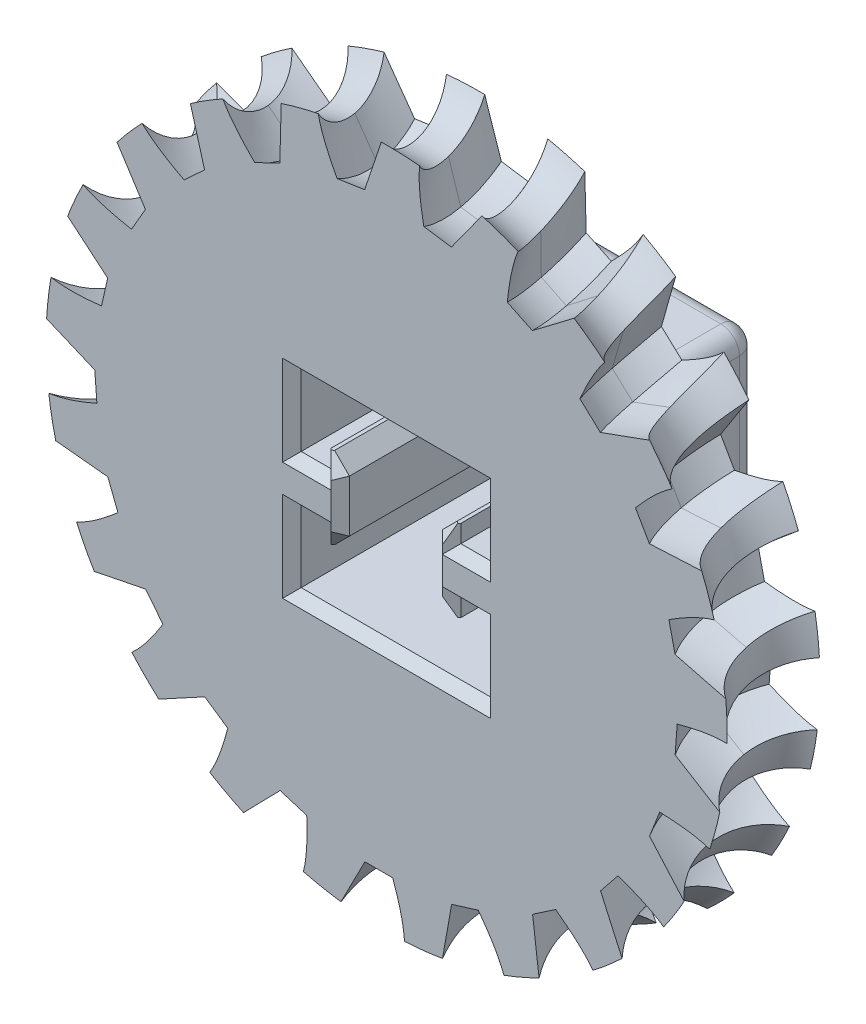
SolidWorks part; units mm, degrees
ref_plane "Front Plane" through (0, 0, 0) normal (0, 0, 1) x (1, 0, 0)
ref_plane "Top Plane" through (0, 0, 0) normal (0, 1, 0) x (1, 0, 0)
ref_plane "Right Plane" through (0, 0, 0) normal (1, 0, 0) x (0, 0, -1)
sketch "Sketch1" plane through (0, 0, 0) normal (0, 0, 1) x (1, 0, 0)
  circle A0 centre (0, 0) radius 40
  circle A1 centre (0, 0) radius 4
  dimension "D1" = 80
  dimension "D2" = 8
extrude "Boss-Extrude1" add sketch "Sketch1" along normal blind 10
chamfer "Chamfer1" distance 2 angle 45 2 edges at (40, 0, 0) (40, 0, 10)
sketch "Sketch2" plane through (0, 0, 0) normal (1, 0, 0) x (0, 0, -1)
  line L0 (0, 0) -> (12.769, 0) construction
  line L1 (0, 0) -> (-5, 0) construction
  line L2 (-5, 0) -> (-5, -40) construction
  circle A0 centre (-5, -40) radius 6
  dimension "D1" = 12
  dimension "D2" = 40
revolve "Cut-Revolve1" cut sketch "Sketch2" angle 360 about L0
sketch "Sketch3" plane through (0, 0, 0) normal (1, 0, 0) x (0, 0, -1)
  circle A1 centre (-5, -40) radius 6
  circle A2 centre (-5, -40) radius 6
  dimension "D1" = 0
curve "Helix/Spiral1" pitch 10 height 2.5 turns 0.25
ref_plane "Plane1" through (0, 0, 5) normal (0, 0, 1) x (1, 0, 0)
sketch "Sketch5" plane through (0, 0, 5) normal (0, 0, 1) x (1, 0, 0)
  line L0 (0, 0) -> (0, -30) construction
  line L1 (-1.5, -30) -> (1.5, -30)
  line L4 (3.5, -34) -> (1.5, -30)
  line L6 (-3.5, -35.5198) -> (3.5, -35.5198)
  line L7 (3.5, -35.5198) -> (3.5, -34)
  line L8 (-3.5, -35.5198) -> (-3.5, -34)
  line L9 (-3.5, -34) -> (-1.5, -30)
  point P9 (0, -35.5198)
  dimension "D1" = 30
  dimension "D2" = 3
  dimension "D3" = 4
  dimension "D4" = 7
sweep "Cut-Sweep1" cut profiles "Sketch5" path "Helix/Spiral1" align with end faces yes
sketch "Sketch6" plane through (0, 0, 0) normal (1, 0, 0) x (0, 0, -1)
  circle A1 centre (-5, -40) radius 6
  circle A2 centre (-5, -40) radius 6
  dimension "D1" = 0
curve "Helix/Spiral2" pitch 10 height 2.5 turns 0.25
sketch "Sketch7" plane through (0, 0, 5) normal (0, 0, 1) x (1, 0, 0)
  line L6 (1.5, -30) -> (-1.5, -30)
  line L7 (3.5, -34) -> (1.5, -30)
  line L8 (3.5, -35.5198) -> (3.5, -34)
  line L9 (-3.5, -35.5198) -> (3.5, -35.5198)
  line L10 (-3.5, -34) -> (-3.5, -35.5198)
  line L11 (-1.5, -30) -> (-3.5, -34)
  line L12 (1.5, -30) -> (-1.5, -30)
  line L13 (3.5, -34) -> (1.5, -30)
  line L14 (3.5, -35.5198) -> (3.5, -34)
  line L15 (-3.5, -35.5198) -> (3.5, -35.5198)
  line L16 (-3.5, -34) -> (-3.5, -35.5198)
  line L17 (-1.5, -30) -> (-3.5, -34)
  dimension "D1" = 0
sweep "Cut-Sweep2" cut profiles "Sketch7" path "Helix/Spiral2" align with end faces yes
pattern_circular "CirPattern1" count 21 over 360 about axis through (0, 0, 10) along (0, 0, -1) of "Cut-Sweep1", "Cut-Sweep2" reverse direction yes
sketch "Sketch14" plane through (0, 0, 0) normal (0, 0, -1) x (-1, 0, 0)
  line L1 (-15, -15) -> (15, -15)
  line L2 (-15, -15) -> (-15, 15)
  line L3 (-15, 15) -> (15, 15)
  line L4 (15, -15) -> (15, 15)
  line L5 (-15, -15) -> (15, 15) construction
  line L6 (-15, 15) -> (15, -15) construction
  point P0 (0, 0)
  dimension "D1" = 30
  dimension "D2" = 30
sketch "Sketch13" plane through (0, 0, 10) normal (0, 0, 1) x (1, 0, 0)
  line L0 (0, -10.2) -> (0, 10.2) construction
  line L1 (10.2, 10.2) -> (-10.2, 10.2) construction
  line L2 (-3.1, 10.2) -> (3.1, 10.2)
  line L3 (-10.2, 10.2) -> (-3.1, 10.2)
  line L9 (-10.2, -10.2) -> (-10.2, 10.2) construction
  line L10 (10.2, 0) -> (-10.2, 0) construction
  line L11 (-5, 2.8) -> (-5, -2.8)
  line L12 (-6.6, 4.4) -> (-5, 2.8)
  line L13 (-7, 4.4) -> (-6.6, 4.4)
  line L14 (-7, 2.5) -> (-7, 4.4)
  line L15 (-10.2, 2.5) -> (-7, 2.5)
  line L16 (-10.2, 10.2) -> (-10.2, 2.5)
  line L17 (10.2, -10.2) -> (10.2, 10.2) construction
  line L18 (10.2, 10.2) -> (0, 0) construction
  line L19 (10.2, 10.2) -> (10.2, 2.5)
  line L20 (10.2, 2.5) -> (7, 2.5)
  line L21 (7, 2.5) -> (7, 4.4)
  line L22 (7, 4.4) -> (6.6, 4.4)
  line L23 (6.6, 4.4) -> (5, 2.8)
  line L24 (5, 2.8) -> (5, -2.8)
  line L29 (10.2, 10.2) -> (3.1, 10.2)
  line L30 (10.2, -10.2) -> (0, 0) construction
  line L31 (-10.2, -10.2) -> (0, 0) construction
  line L32 (10.2, -10.2) -> (-10.2, -10.2) construction
  line L33 (10.2, -10.2) -> (3.1, -10.2)
  line L38 (6.6, -4.4) -> (5, -2.8)
  line L39 (7, -4.4) -> (6.6, -4.4)
  line L40 (7, -2.5) -> (7, -4.4)
  line L41 (10.2, -2.5) -> (7, -2.5)
  line L42 (10.2, -10.2) -> (10.2, -2.5)
  line L43 (-10.2, -10.2) -> (-10.2, -2.5)
  line L44 (-10.2, -2.5) -> (-7, -2.5)
  line L45 (-7, -2.5) -> (-7, -4.4)
  line L46 (-7, -4.4) -> (-6.6, -4.4)
  line L47 (-6.6, -4.4) -> (-5, -2.8)
  line L53 (-10.2, -10.2) -> (-3.1, -10.2)
  line L54 (-3.1, -10.2) -> (3.1, -10.2)
  point P4 (-7, 3.45)
  point P27 (0, 4)
  point P40 (5, 0)
  point P49 (-5, 0)
  point P54 (0, -4)
  dimension "D1" = 10.2
  dimension "D2" = 10.2
  dimension "D3" = 5
  dimension "D4" = 3.2
  dimension "D5" = 135
  dimension "D6" = 2
  dimension "D7" = 1.9
  dimension "D8" = 2.8
extrude "Boss-Extrude2" add sketch "Sketch14" along normal blind 15 contours L3 L4 L1 L2
extrude "Cut-Extrude4" cut sketch "Sketch13" against normal up to surface (25 mm away) up to face at (0, 0, -15)
sketch "Sketch15" plane through (0, 15, 0) normal (0, 1, 0) x (1, 0, 0)
  line L0 (15, 7.5) -> (-15, 7.5) construction
  line L3 (15, 15) -> (15, 0) construction
  line L4 (-15, 15) -> (-15, 0) construction
  circle A1 centre (0, 7.5) radius 2
extrude "Cut-Extrude3" cut sketch "Sketch15" against normal up to surface (30 mm away) up to face at (0, -15, -7.5)
fillet "Fillet1" radius 2 13 edges at (0, 15, 0) (0, -15, -15) (0, -15, 0) (15, 15, -7.5) (15, 0, -15) (15, -15, -7.5) (15, 0, 0) (-15, -15, -7.5) (-15, 0, -15) (-15, 15, -7.5) (-15, 0, 0) (0, 15, -15) (0, -15, -5.5)
chamfer "Chamfer2" distance 1 angle 45 41 edges at (-10.2, 6.35, 10) (-8.6, 2.5, 10) (-7, 3.45, 10) (-5.8, 3.6, 10) (-5, 0, 10) (-5.8, -3.6, 10) (-7, -3.45, 10) (-8.6, -2.5, 10) (-10.2, -6.35, 10) (0, -10.2, 10) (10.2, -6.35, 10) (8.6, -2.5, 10) (7, -3.45, 10) (5.8, -3.6, 10) (5, 0, 10) (5.8, 3.6, 10) (7, 3.45, 10) (8.6, 2.5, 10) (10.2, 6.35, 10) (0, 10.2, 10) (10.2, 6.35, -15) (8.6, 2.5, -15) (7, 3.45, -15) (5.8, 3.6, -15) (5, 0, -15) (5.8, -3.6, -15) (7, -3.45, -15) (8.6, -2.5, -15) (10.2, -6.35, -15) (0, -10.2, -15) (-10.2, -6.35, -15) (-8.6, -2.5, -15) (-7, -3.45, -15) (-5.8, -3.6, -15) (-5, 0, -15) (-5.8, 3.6, -15) (-7, 3.45, -15) (-8.6, 2.5, -15) (-10.2, 6.35, -15) (0, 10.2, -15) (0, 15, -5.5)
